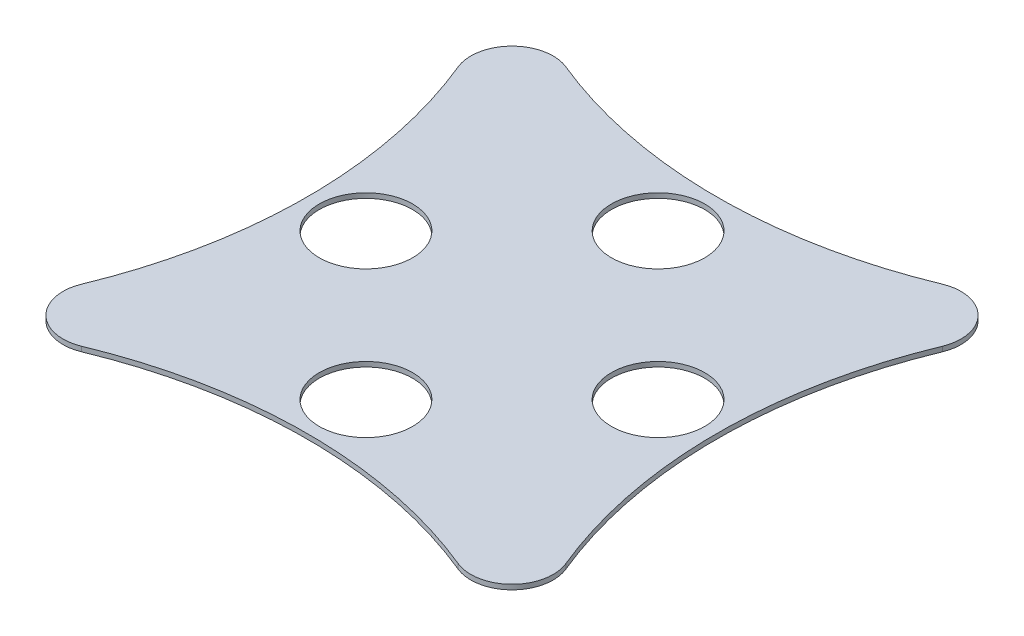
SolidWorks part; units mm, degrees
ref_plane "Front Plane" through (0, 0, 0) normal (0, 0, 1) x (1, 0, 0)
ref_plane "Top Plane" through (0, 0, 0) normal (0, 1, 0) x (1, 0, 0)
ref_plane "Right Plane" through (0, 0, 0) normal (1, 0, 0) x (0, 0, -1)
sketch "Sketch2" plane through (0, 0, 0) normal (0, 1, 0) x (1, 0, 0)
  line L0 (-212.132, -212.132) -> (212.132, 212.132) construction
  line L1 (-212.132, 212.132) -> (212.132, -212.132) construction
  arc A0 (-212.132, 212.132) -> (212.132, 212.132) centre (0, 430.9997) ccw
  arc A1 (212.132, 212.132) -> (212.132, -212.132) centre (430.9997, 0) ccw
  arc A2 (-212.132, -212.132) -> (212.132, -212.132) centre (0, -430.9997) cw
  arc A3 (-212.132, 212.132) -> (-212.132, -212.132) centre (-430.9997, 0) cw
  point P4 (0, 0)
  point P5 (0, 0)
  dimension "D2" = 304.8
  dimension "D1" = 469.2528
  dimension "D3" = 600
extrude "Boss-Extrude1" add sketch "Sketch2" along normal blind 3 contours A0 A3 A2 A1 region at (0, 0, 0)
fillet "Fillet1" radius 25.4 4 edges at (212.132, 1.5, -212.132) (212.132, 1.5, 212.132) (-212.132, 1.5, -212.132) (-212.132, 1.5, 212.132)
ref_axis "Axis1" through (0, 3.15, 0) along (0, -1, 0)
sketch "Sketch3" plane through (0, 3, 0) normal (0, 1, 0) x (1, 0, 0)
  line L0 (0, 0) -> (90, 0) construction
  circle A0 centre (90, 0) radius 28.75
  dimension "D1" = 57.5
  dimension "D2" = 90
extrude "Cut-Extrude1" cut sketch "Sketch3" against normal through all
pattern_circular "CirPattern1" count 4 every 90 about axis through (0, 3.15, 0) along (0, -1, 0) of "Cut-Extrude1"
